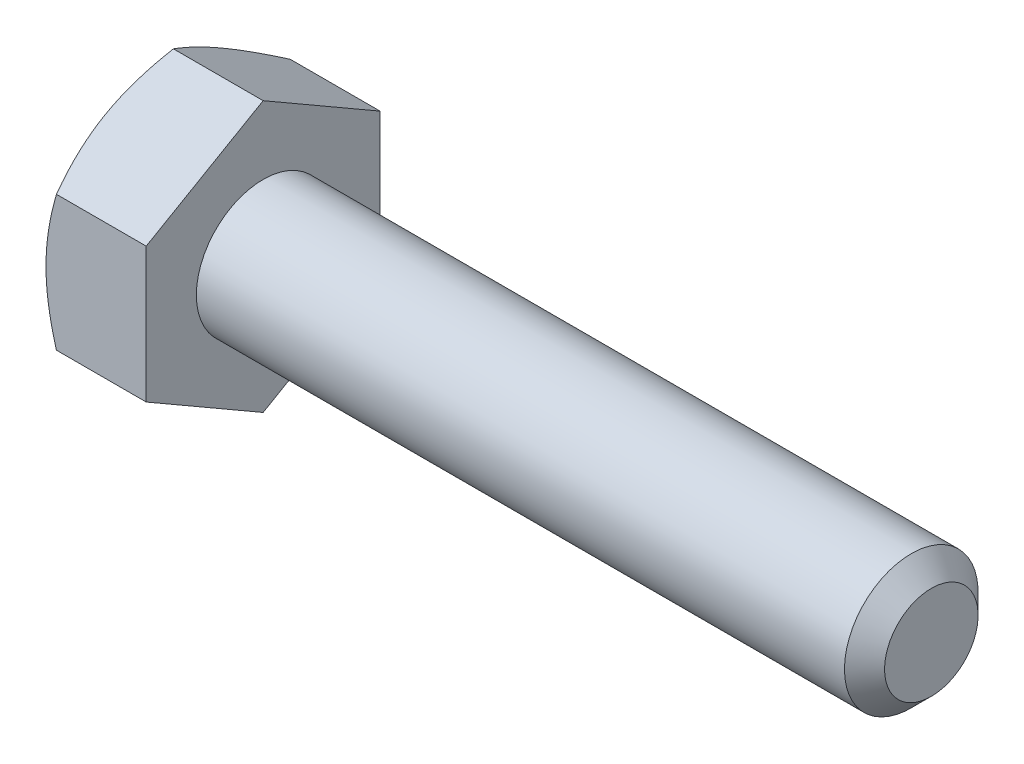
SolidWorks part; units mm, degrees
material "AISI 304"
ref_plane "Front Plane" through (0, 0, 0) normal (0, 0, 1) x (1, 0, 0)
ref_plane "Top Plane" through (0, 0, 0) normal (0, 1, 0) x (1, 0, 0)
ref_plane "Right Plane" through (0, 0, 0) normal (1, 0, 0) x (0, 0, -1)
sketch "Sketch1" plane through (0, 0, 0) normal (0, 0, 1) x (1, 0, 0)
  line L0 (-18.2563, 0) -> (18.2563, 0) construction
  line L1 (18.2563, 3.175) -> (18.2563, -3.175) construction
  line L2 (-13.4938, 5.5562) -> (-13.4938, -5.5562) construction
  line L3 (-18.2563, 5.5562) -> (-18.2563, -5.5562) construction
  point P9 (-13.4938, 0)
  point P10 (13.8113, -3.175)
  dimension "Screw Dia" = 6.35
  dimension "Hex" = 11.1125
  dimension "Head Ht" = 4.7625
  dimension "Screw Lenght" = 31.75
  dimension "D1" = 4.445
ref_plane "Plane2" through (18.2563, 0, 0) normal (1, 0, 0) x (0, 0, -1)
sketch "Sketch5" plane through (18.2563, 0, 0) normal (1, 0, 0) x (0, 0, -1)
  circle A0 centre (0, 0) radius 3.175
extrude "Boss-Extrude3" add sketch "Sketch5" against normal up to vertex (31.75 mm away) up to point (-13.4938, 0, 0)
sketch "Sketch9" plane through (18.2563, 0, 0) normal (1, 0, 0) x (0, 0, -1)
  circle A1 centre (0, 0) radius 3.175
  circle A2 centre (0, 0) radius 3.175
  dimension "D1" = 0
curve "Helix/Spiral1" pitch 1.27 height 33.02 turns 26 parameters "Pitch"=1.27
chamfer "Chamfer1" distance 0.9525 angle 45 1 edges at (18.2563, 0, -3.175)
sketch "Sketch10" plane through (0, 0, 0) normal (0, 0, 1) x (1, 0, 0)
  line L0 (18.2563, 3.175) -> (18.7325, 2.3501)
  line L1 (18.7325, 2.3501) -> (18.8912, 2.3501)
  line L2 (18.8912, 2.3501) -> (19.3675, 3.175)
  line L3 (18.2563, 3.175) -> (19.3675, 3.175)
  line L4 (18.8119, 3.175) -> (18.8119, 2.3501) construction
  line L5 (18.4944, 2.7626) -> (19.1294, 2.7626) construction
  dimension "D1" = 60
  dimension "D2" = 0.1588
  dimension "D3" = 0.635
sweep "Cut-Sweep1" [suppressed] cut profiles "Sketch10" path "Helix/Spiral1"
sketch "Sketch6" plane through (-13.4937, 0, 0) normal (-1, 0, 0) x (0, 0, 1)
  line L0 (0, 5.5562) -> (0, -5.5562) construction
  line L1 (5.5562, 3.2079) -> (0, 6.4158)
  line L2 (0, 6.4158) -> (-5.5562, 3.2079)
  line L3 (-5.5562, 3.2079) -> (-5.5562, -3.2079)
  line L4 (-5.5562, -3.2079) -> (0, -6.4158)
  line L5 (0, -6.4158) -> (5.5562, -3.2079)
  line L6 (5.5562, -3.2079) -> (5.5562, 3.2079)
  circle A0 centre (0, 0) radius 5.5562 construction
extrude "Boss-Extrude4" add sketch "Sketch6" along normal up to vertex (4.7625 mm away) up to point (-18.2563, -5.5562, 0)
sketch "Sketch7" plane through (-18.2563, 0, 0) normal (-1, 0, 0) x (0, 0, 1)
  circle A0 centre (0, 0) radius 5.5562 construction
  circle A1 centre (0, 0) radius 5.5562
sketch "Sketch8" plane through (-18.2563, 0, 0) normal (-1, 0, 0) x (0, 0, 1)
  circle A0 centre (0, 0) radius 5.5562 construction
  circle A1 centre (0, 0) radius 5.5562
extrude "Cut-Extrude3" cut sketch "Sketch8" against normal through all draft 60 flip side to cut
sketch "Sketch12" plane through (-18.2563, 0, 0) normal (-1, 0, 0) x (0, 0, 1)
  line L0 (0, 4.2783) -> (0, 2.3892) construction
  line L1 (0.1667, 4.2783) -> (0.1667, 2.3892)
  line L2 (-0.1667, 4.2783) -> (-0.1667, 2.3892)
  line L3 (0, 3.175) -> (0, -3.175) construction
  arc A0 (0.1667, 4.2783) -> (-0.1667, 4.2783) centre (0, 4.2783) ccw
  arc A1 (-0.1667, 2.3892) -> (0.1667, 2.3892) centre (0, 2.3892) ccw
  circle A3 centre (0, 0) radius 2.2225 construction
  circle A4 centre (0, 0) radius 4.445 construction
  point P2 (0, 3.3337)
  dimension "D1" = 4.445
  dimension "D3" = 8.89
  dimension "D2" = 0.3334
extrude "Cut-Extrude4" [suppressed] cut sketch "Sketch12" against normal blind 0.254
pattern_circular "CirPattern1" [suppressed] count 9 over 360 of bodies 116
equation "\"D2@Sketch10\" = \"Pitch@Helix/Spiral1\"*.125"
equation "\"D3@Sketch10\" = \"Pitch@Helix/Spiral1\"*.5"
equation "\"D3@Helix/Spiral1\" = \"Screw Lenght@Sketch1\"+\"Pitch@Helix/Spiral1\""
equation "\"D1@Chamfer1\" = \"Pitch@Helix/Spiral1\"*.75"
equation "\"D1@Sketch12\" = \"Hex@Sketch1\"*.4"
equation "\"D3@Sketch12\" = \"Hex@Sketch1\"*.8"
equation "\"D2@Sketch12\" = \"Hex@Sketch1\"*.03"
equation "\"D1@Sketch1\" = \"Pitch@Helix/Spiral1\"*3.5"
